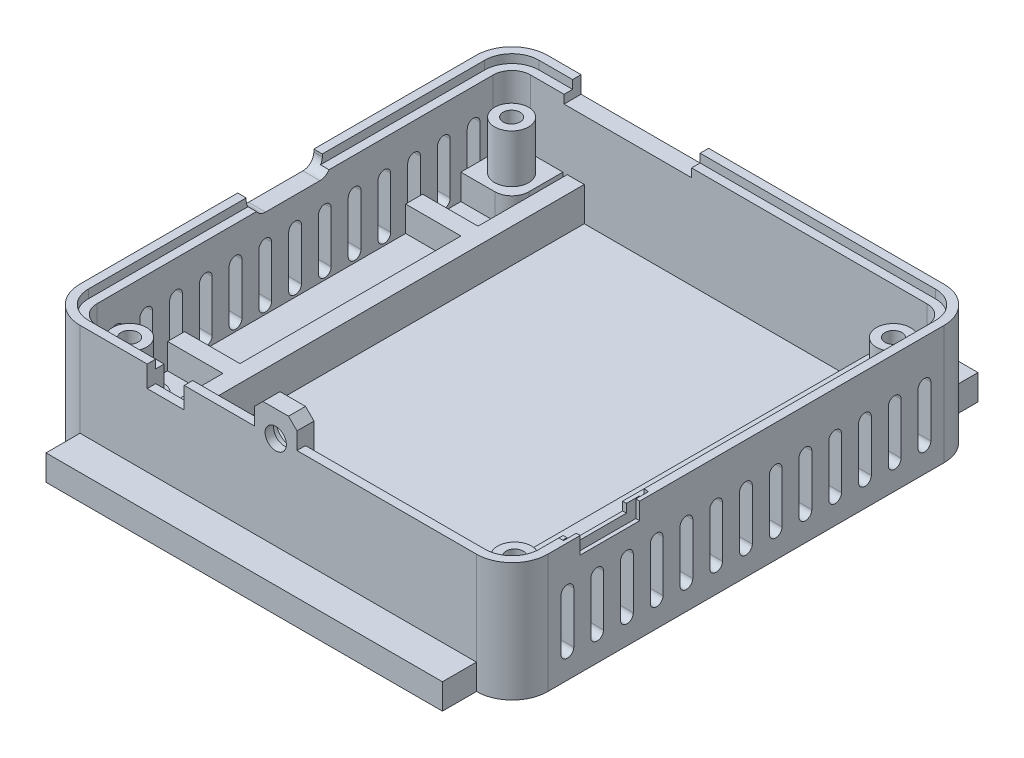
SolidWorks part; units mm, degrees
ref_plane "Front Plane" through (0, 0, 0) normal (0, 0, 1) x (1, 0, 0)
ref_plane "Top Plane" through (0, 0, 0) normal (0, 1, 0) x (1, 0, 0)
ref_plane "Right Plane" through (0, 0, 0) normal (1, 0, 0) x (0, 0, -1)
sketch "Sketch2" plane through (0, 0, 0) normal (0, 1, 0) x (1, 0, 0)
  line L0 (-26.515, 23.3) -> (-26.515, -23.3)
  line L1 (-23.315, 25.5) -> (23.315, 25.5)
  line L2 (-25.515, 23.3) -> (-25.515, -23.3)
  line L3 (-23.315, -25.5) -> (23.315, -25.5)
  line L4 (25.515, 23.3) -> (25.515, -23.3)
  line L5 (-25.515, 25.5) -> (25.515, -25.5) construction
  line L6 (-25.515, -25.5) -> (25.515, 25.5) construction
  line L7 (-23.315, -26.5) -> (23.315, -26.5)
  line L8 (26.515, 23.3) -> (26.515, -23.3)
  line L9 (-23.315, 26.5) -> (23.315, 26.5)
  line L10 (-27.515, 23.3) -> (-27.515, -23.3)
  line L11 (-23.315, -27.5) -> (23.315, -27.5)
  line L12 (27.515, 23.3) -> (27.515, -23.3)
  line L13 (-23.315, 27.5) -> (23.315, 27.5)
  line L14 (-25.515, 19.5) -> (-21.515, 19.5)
  line L15 (-19.515, 21.5) -> (-19.515, 25.5)
  line L16 (19.515, 25.5) -> (19.515, 21.5)
  line L17 (21.515, 19.5) -> (25.515, 19.5)
  line L18 (-25.515, -19.5) -> (-21.515, -19.5)
  line L19 (-19.515, -21.5) -> (-19.515, -25.5)
  line L20 (19.515, -25.5) -> (19.515, -21.5)
  line L21 (21.515, -19.5) -> (25.515, -19.5)
  arc A0 (23.315, 25.5) -> (25.515, 23.3) centre (23.315, 23.3) cw
  arc A1 (25.515, -23.3) -> (23.315, -25.5) centre (23.315, -23.3) cw
  arc A2 (-23.315, -25.5) -> (-25.515, -23.3) centre (-23.315, -23.3) cw
  arc A3 (-23.315, 25.5) -> (-25.515, 23.3) centre (-23.315, 23.3) ccw
  arc A4 (-23.315, -26.5) -> (-26.515, -23.3) centre (-23.315, -23.3) cw
  arc A5 (26.515, -23.3) -> (23.315, -26.5) centre (23.315, -23.3) cw
  arc A6 (23.315, 26.5) -> (26.515, 23.3) centre (23.315, 23.3) cw
  arc A7 (-23.315, 26.5) -> (-26.515, 23.3) centre (-23.315, 23.3) ccw
  arc A8 (-23.315, -27.5) -> (-27.515, -23.3) centre (-23.315, -23.3) cw
  arc A9 (27.515, -23.3) -> (23.315, -27.5) centre (23.315, -23.3) cw
  arc A10 (23.315, 27.5) -> (27.515, 23.3) centre (23.315, 23.3) cw
  arc A11 (-23.315, 27.5) -> (-27.515, 23.3) centre (-23.315, 23.3) ccw
  circle A12 centre (-22.455, 22.41) radius 1
  circle A13 centre (22.445, 22.42) radius 1
  circle A14 centre (22.425, -22.11) radius 1
  circle A15 centre (-22.495, -22.49) radius 1
  arc A20 (21.515, -19.5) -> (19.515, -21.5) centre (21.515, -21.5) ccw
  arc A21 (-19.515, -21.5) -> (-21.515, -19.5) centre (-21.515, -21.5) ccw
  arc A22 (-19.515, 21.5) -> (-21.515, 19.5) centre (-21.515, 21.5) cw
  arc A23 (21.515, 19.5) -> (19.515, 21.5) centre (21.515, 21.5) cw
  point P0 (0, 0)
  point P64 (-20.015, -20)
  point P65 (19.515, -19.5)
  point P67 (20.015, -20)
  point P69 (-19.515, -19.5)
  point P70 (20.015, 20)
  point P73 (-20.015, 20)
  point P74 (-19.515, 19.5)
  point P77 (19.515, 19.5)
  dimension "D3" = 2.2
  dimension "D6" = 3.09
  dimension "D7" = 3.06
  dimension "D8" = 2
  dimension "D9" = 2
  dimension "D10" = 3.07
  dimension "D11" = 3.08
  dimension "D12" = 2
  dimension "D13" = 3.39
  dimension "D14" = 3.09
  dimension "D15" = 3.01
  dimension "D16" = 3.02
  dimension "D17" = 2
  dimension "D28" = 2
  dimension "D29" = 55.03
  dimension "D30" = 55
  dimension "D18" = 6
  dimension "D19" = 6
  dimension "D20" = 6
  dimension "D21" = 6
  dimension "D1" = 51.03
  dimension "D2" = 51
  dimension "D5" = 2
  dimension "D22" = 6
  dimension "D23" = 6
  dimension "D24" = 6
  dimension "D25" = 6
  dimension "D26" = 1
  dimension "D27" = 1
  dimension "D4" = 1
extrude "Boss-Extrude1" add sketch "Sketch2" along normal blind 14 contours L13 A11 L10 A8 L11 A9 L12 A10 A7 L9 A6 L8 A5 L7 A4 L0 region at (-25.7347, 0, -25.7197)
extrude "Boss-Extrude2" add sketch "Sketch2<3>" along normal blind 13 contours L9 A7 L0 A4 L7 A5 L8 A6 A3 L1 A0 L4 A1 L3 A2 L2 region at (-25.0476, 0, -25.0326)
sketch "Sketch2<3>" plane through (0, 0, 0) normal (0, 1, 0) x (1, 0, 0) same geometry as "Sketch2"
extrude "Boss-Extrude4" add sketch "Sketch2<5>" along normal blind 2 contours L2 L3 L4 L1 region at (0, 0, 0)
sketch "Sketch2<5>" plane through (0, 0, 0) normal (0, 1, 0) x (1, 0, 0) same geometry as "Sketch2"
sketch "Sketch4" plane through (0, 0, -27.5) normal (0, 0, -1) x (-1, 0, 0)
  line L0 (23.315, 14) -> (-23.315, 14) construction
  line L1 (19.375, 12) -> (4.375, 12)
  line L2 (19.375, 12) -> (19.375, 14)
  line L3 (19.375, 14) -> (4.375, 14)
  line L4 (4.375, 12) -> (4.375, 14)
  line L5 (19.375, 12) -> (4.375, 14) construction
  line L6 (19.375, 14) -> (4.375, 12) construction
  line L7 (27.515, 14) -> (27.515, 0) construction
  point P0 (11.875, 13)
  dimension "D1" = 8.14
  dimension "D2" = 15
  dimension "D3" = 2
extrude "Cut-Extrude1" cut sketch "Sketch4" against normal blind 2
sketch "Sketch6" plane through (-27.515, 0, 0) normal (-1, 0, 0) x (0, 0, 1)
  line L0 (-23.3, 14) -> (23.3, 14) construction
  line L1 (-4.2, 14) -> (4.75, 14)
  line L2 (-4.2, 14) -> (-4.2, 13.7)
  line L3 (-2.92, 12.42) -> (3.47, 12.42)
  line L4 (4.75, 14) -> (4.75, 13.7)
  line L5 (-27.5, 14) -> (-27.5, 0) construction
  line L6 (27.5, 14) -> (27.5, 0) construction
  arc A0 (4.75, 13.7) -> (3.47, 12.42) centre (3.47, 13.7) cw
  arc A1 (-2.92, 12.42) -> (-4.2, 13.7) centre (-2.92, 13.7) cw
  point P10 (4.75, 12.42)
  point P13 (-4.2, 12.42)
  dimension "D4" = 1.28
  dimension "D1" = 23.3
  dimension "D2" = 1.58
  dimension "D3" = 8.95
  dimension "D5" = 22.75
extrude "Cut-Extrude3" cut sketch "Sketch6" against normal blind 2
sketch "Sketch7" plane through (0, 0, 27.5) normal (0, 0, 1) x (1, 0, 0)
  line L0 (-23.315, 0) -> (23.315, 0) construction
  line L1 (27.515, 14) -> (27.515, 0) construction
  line L2 (0, 0) -> (0, 27.9568) construction
  line L3 (-27.515, 14) -> (-27.515, 0) construction
  circle A0 centre (-0.29, 13.97) radius 1.25
  dimension "D1" = 27.225
  dimension "D2" = 2.5
  dimension "D3" = 13.97
  dimension "D4" = 27.805
extrude "Cut-Extrude4" cut sketch "Sketch7" against normal blind 2
sketch "Sketch8" plane through (0, 0, 25.5) normal (0, 0, -1) x (-1, 0, 0)
  circle A0 centre (0.29, 13.97) radius 2
  dimension "D1" = 4
sketch "Sketch9" plane through (0, 2, 0) normal (0, 1, 0) x (1, 0, 0)
  line L0 (-17, 25.5) -> (-17, -25.5)
  line L1 (-19.515, 25.5) -> (19.515, 25.5) construction
  line L2 (-19.515, -25.5) -> (19.515, -25.5) construction
  line L3 (17, 25.5) -> (17, -25.5)
  line L4 (-25.515, 19.5) -> (-25.515, -19.5) construction
  line L5 (25.515, 19.5) -> (25.515, -19.5) construction
  line L6 (-19, 25.5) -> (-19, 15)
  line L7 (19, 25.5) -> (19, 15)
  line L8 (-19, 25.5) -> (-17, 25.5)
  line L9 (-19, -25.5) -> (-17, -25.5)
  line L10 (17, -25.5) -> (19, -25.5)
  line L11 (17, 25.5) -> (19, 25.5)
  line L13 (-25.515, 19.5) -> (-25.515, -19.5) construction
  line L14 (-25.515, 15) -> (-19, 15)
  line L15 (-25.515, 15) -> (-25.515, 13)
  line L16 (-25.515, 13) -> (-19, 13)
  line L17 (25.515, 15) -> (25.515, 13)
  line L18 (25.515, 23.3) -> (25.515, -23.3) construction
  line L19 (-25.515, -4.5416) -> (-25.515, -23.3) construction
  line L20 (-25.515, -13) -> (-19, -13)
  line L21 (-25.515, -13) -> (-25.515, -15)
  line L22 (-25.515, -15) -> (-19, -15)
  line L23 (25.515, -13) -> (25.515, -15)
  line L24 (19, 15) -> (25.515, 15)
  line L25 (19, 13) -> (25.515, 13)
  line L26 (19, -13) -> (25.515, -13)
  line L27 (19, -15) -> (25.515, -15)
  line L28 (-19.515, 25.5) -> (19.515, 25.5) construction
  line L29 (-19.515, -25.5) -> (19.515, -25.5) construction
  line L30 (-4.375, 25.5) -> (23.315, 25.5) construction
  line L31 (-19, 13) -> (-19, -13)
  line L32 (-19, 25.5) -> (-19, -25.5) construction
  line L33 (-19, -15) -> (-19, -25.5)
  line L34 (19, -15) -> (19, -25.5)
  line L35 (19, 25.5) -> (19, -25.5) construction
  line L36 (19, 13) -> (19, -13)
  dimension "D1" = 34
  dimension "D2" = 8.515
  dimension "D3" = 8.515
  dimension "D6" = 2
  dimension "D7" = 2
  dimension "D8" = 2
  dimension "D9" = 2
  dimension "D10" = 10.5
  dimension "D11" = 10.5
  dimension "D12" = 26
  dimension "D13" = 10.5
  dimension "D14" = 26
  dimension "D15" = 10.5
  dimension "D4" = 2
  dimension "D5" = 2
extrude "Boss-Extrude6" add sketch "Sketch9" along normal blind 3
extrude "Boss-Extrude9" add sketch "Sketch2<7>" along normal blind 5 contours A12 | A13 | A15 | A14 region at (-21.415, 0, -25.4151) region at (21.415, 0, -25.4151) region at (-23.515, 0, 19.5849) region at (25.4301, 0, 21.4)
sketch "Sketch2<7>" plane through (0, 0, 0) normal (0, 1, 0) x (1, 0, 0) same geometry as "Sketch2"
sketch "Sketch11" plane through (0, 5, 0) normal (0, 1, 0) x (1, 0, 0)
  circle A0 centre (-22.455, 22.41) radius 1
  circle A1 centre (-22.455, 22.41) radius 2
  circle A2 centre (22.445, 22.42) radius 1
  circle A3 centre (22.445, 22.42) radius 2
  circle A6 centre (-22.495, -22.49) radius 1
  circle A7 centre (-22.495, -22.49) radius 2
  circle A8 centre (22.425, -22.11) radius 1
  circle A9 centre (22.425, -22.11) radius 2
  dimension "D1" = 2
  dimension "D2" = 4
  dimension "D3" = 2
  dimension "D4" = 4
  dimension "D5" = 2
  dimension "D6" = 4
  dimension "D7" = 2
  dimension "D8" = 4
extrude "Boss-Extrude10" add sketch "Sketch11" along normal blind 5.68
sketch "Sketch13" plane through (0, 0, 27.5) normal (0, 0, 1) x (1, 0, 0)
  line L0 (27.515, 14) -> (27.515, 0) construction
  line L5 (-27.515, 14) -> (-27.515, 0) construction
  line L7 (0.9596, 14) -> (23.315, 14) construction
  line L8 (-2.79, 17) -> (2.21, 17)
  line L9 (-2.79, 17) -> (-2.79, 14)
  line L10 (-2.79, 14) -> (-1.5396, 14)
  line L11 (2.21, 17) -> (2.21, 14)
  line L12 (-2.79, 17) -> (2.21, 14) construction
  line L13 (-2.79, 14) -> (2.21, 17) construction
  line L14 (0.9596, 14) -> (2.21, 14)
  arc A0 (0.9596, 14) -> (-1.5396, 14) centre (-0.29, 13.97) ccw
  point P0 (-0.29, 15.5)
  dimension "D4" = 0.03
  dimension "D5" = 2.5
  dimension "D7" = 2.5
  dimension "D1" = 5
  dimension "D2" = 25.305
  dimension "D3" = 3
  dimension "D6" = 24.725
extrude "Boss-Extrude11" add sketch "Sketch13" against normal blind 2
sketch "Sketch15" plane through (0, 0, 26.5) normal (0, 0, -1) x (-1, 0, 0)
  line L0 (-1.459, 13) -> (-1.459, 14)
  line L1 (-2.21, 14) -> (-2.21, 13)
  line L2 (-2.21, 13) -> (-1.459, 13)
  line L3 (-1.459, 14) -> (-2.21, 14)
  line L4 (2.039, 13) -> (2.039, 14)
  line L5 (2.79, 14) -> (2.79, 13)
  line L6 (2.039, 14) -> (2.79, 14)
  line L7 (2.79, 13) -> (2.039, 13)
  dimension "D1" = 1
  dimension "D2" = 1
  dimension "D3" = 0.751
  dimension "D4" = 1
  dimension "D5" = 1
  dimension "D6" = 0.751
extrude "Boss-Extrude13" add sketch "Sketch15" along normal blind 1
extrude "Cut-Extrude5" cut sketch "Sketch8" against normal blind 1
sketch "Sketch16" plane through (0, 2, 0) normal (0, 1, 0) x (1, 0, 0)
  line L1 (-17, 25.5) -> (17, 25.5)
  line L2 (-17, 25.5) -> (-17, -25.5)
  line L3 (-17, -25.5) -> (17, -25.5)
  line L4 (17, 25.5) -> (17, -25.5)
  line L5 (-17, 25.5) -> (17, -25.5) construction
  line L6 (-17, -25.5) -> (17, 25.5) construction
  point P0 (0, 0)
extrude "Cut-Extrude6" cut sketch "Sketch16" against normal blind 1
sketch "Sketch17" plane through (0, 0, 0) normal (0, -1, 0) x (1, 0, 0)
  circle A0 centre (-22.495, 22.49) radius 2
  circle A1 centre (22.425, 22.11) radius 2
  circle A2 centre (-22.455, -22.41) radius 2
  circle A3 centre (22.445, -22.42) radius 2
  dimension "D1" = 4
  dimension "D2" = 4
  dimension "D3" = 4
  dimension "D4" = 4
extrude "Cut-Extrude7" cut sketch "Sketch17" against normal blind 3
sketch "Sketch19" plane through (27.515, 0, 0) normal (1, 0, 0) x (0, 0, -1)
  line L0 (23.3, 14) -> (-23.3, 14) construction
  line L2 (-21.75, 9) -> (-21.75, 3)
  line L4 (-20.25, 9) -> (-20.25, 3)
  line L5 (-27.5, 14) -> (-27.5, 0) construction
  line L6 (23.3, 0) -> (-23.3, 0) construction
  line L7 (-18.25, 9) -> (-18.25, 3)
  line L8 (-16.75, 9) -> (-16.75, 3)
  line L9 (-14.75, 9) -> (-14.75, 3)
  line L10 (-13.25, 9) -> (-13.25, 3)
  line L11 (-11.25, 9) -> (-11.25, 3)
  line L12 (-9.75, 9) -> (-9.75, 3)
  line L13 (-7.75, 9) -> (-7.75, 3)
  line L14 (-6.25, 9) -> (-6.25, 3)
  line L15 (-4.25, 9) -> (-4.25, 3)
  line L16 (-2.75, 9) -> (-2.75, 3)
  line L17 (-0.75, 9) -> (-0.75, 3)
  line L18 (0.75, 9) -> (0.75, 3)
  line L19 (2.75, 9) -> (2.75, 3)
  line L20 (4.25, 9) -> (4.25, 3)
  line L21 (6.25, 9) -> (6.25, 3)
  line L22 (7.75, 9) -> (7.75, 3)
  line L23 (9.75, 9) -> (9.75, 3)
  line L24 (11.25, 9) -> (11.25, 3)
  line L25 (13.25, 9) -> (13.25, 3)
  line L26 (14.75, 9) -> (14.75, 3)
  line L27 (16.75, 9) -> (16.75, 3)
  line L28 (18.25, 9) -> (18.25, 3)
  line L29 (20.25, 9) -> (20.25, 3)
  line L30 (21.75, 9) -> (21.75, 3)
  line L31 (27.5, 14) -> (27.5, 0) construction
  arc A0 (-21.75, 9) -> (-20.25, 9) centre (-21, 9) cw
  arc A1 (-21.75, 3) -> (-20.25, 3) centre (-21, 3) ccw
  arc A2 (-18.25, 3) -> (-16.75, 3) centre (-17.5, 3) ccw
  arc A3 (-18.25, 9) -> (-16.75, 9) centre (-17.5, 9) cw
  arc A4 (-14.75, 3) -> (-13.25, 3) centre (-14, 3) ccw
  arc A5 (-14.75, 9) -> (-13.25, 9) centre (-14, 9) cw
  arc A6 (-11.25, 3) -> (-9.75, 3) centre (-10.5, 3) ccw
  arc A7 (-11.25, 9) -> (-9.75, 9) centre (-10.5, 9) cw
  arc A8 (-7.75, 3) -> (-6.25, 3) centre (-7, 3) ccw
  arc A9 (-7.75, 9) -> (-6.25, 9) centre (-7, 9) cw
  arc A10 (-4.25, 3) -> (-2.75, 3) centre (-3.5, 3) ccw
  arc A11 (-4.25, 9) -> (-2.75, 9) centre (-3.5, 9) cw
  arc A12 (-0.75, 3) -> (0.75, 3) centre (0, 3) ccw
  arc A13 (-0.75, 9) -> (0.75, 9) centre (0, 9) cw
  arc A14 (2.75, 3) -> (4.25, 3) centre (3.5, 3) ccw
  arc A15 (2.75, 9) -> (4.25, 9) centre (3.5, 9) cw
  arc A16 (6.25, 3) -> (7.75, 3) centre (7, 3) ccw
  arc A17 (6.25, 9) -> (7.75, 9) centre (7, 9) cw
  arc A18 (9.75, 3) -> (11.25, 3) centre (10.5, 3) ccw
  arc A19 (9.75, 9) -> (11.25, 9) centre (10.5, 9) cw
  arc A20 (13.25, 3) -> (14.75, 3) centre (14, 3) ccw
  arc A21 (13.25, 9) -> (14.75, 9) centre (14, 9) cw
  arc A22 (16.75, 3) -> (18.25, 3) centre (17.5, 3) ccw
  arc A23 (16.75, 9) -> (18.25, 9) centre (17.5, 9) cw
  arc A24 (20.25, 3) -> (21.75, 3) centre (21, 3) ccw
  arc A25 (20.25, 9) -> (21.75, 9) centre (21, 9) cw
  dimension "D3" = 0.75
  dimension "D1" = 6
  dimension "D2" = 1.5
  dimension "D4" = 5
  dimension "D5" = 5.75
  dimension "D6" = 3
  dimension "D8" = 5.75
  dimension "D7" = 13
extrude "Cut-Extrude9" cut sketch "Sketch19" against normal blind 2
sketch "Sketch20" plane through (-27.515, 0, 0) normal (-1, 0, 0) x (0, 0, 1)
  line L0 (-23.3, 14) -> (-4.2, 14) construction
  line L2 (-21.75, 9) -> (-21.75, 3)
  line L4 (-20.25, 9) -> (-20.25, 3)
  line L5 (-23.3, 0) -> (23.3, 0) construction
  line L6 (-27.5, 14) -> (-27.5, 0) construction
  line L7 (-18.25, 9) -> (-18.25, 3)
  line L8 (-16.75, 9) -> (-16.75, 3)
  line L9 (-14.75, 9) -> (-14.75, 3)
  line L10 (-13.25, 9) -> (-13.25, 3)
  line L11 (-11.25, 9) -> (-11.25, 3)
  line L12 (-9.75, 9) -> (-9.75, 3)
  line L13 (-7.75, 9) -> (-7.75, 3)
  line L14 (-6.25, 9) -> (-6.25, 3)
  line L15 (-4.25, 9) -> (-4.25, 3)
  line L16 (-2.75, 9) -> (-2.75, 3)
  line L17 (-0.75, 9) -> (-0.75, 3)
  line L18 (0.75, 9) -> (0.75, 3)
  line L19 (2.75, 9) -> (2.75, 3)
  line L20 (4.25, 9) -> (4.25, 3)
  line L21 (6.25, 9) -> (6.25, 3)
  line L22 (7.75, 9) -> (7.75, 3)
  line L23 (9.75, 9) -> (9.75, 3)
  line L24 (11.25, 9) -> (11.25, 3)
  line L25 (13.25, 9) -> (13.25, 3)
  line L26 (14.75, 9) -> (14.75, 3)
  line L27 (16.75, 9) -> (16.75, 3)
  line L28 (18.25, 9) -> (18.25, 3)
  line L29 (20.25, 9) -> (20.25, 3)
  line L30 (21.75, 9) -> (21.75, 3)
  line L31 (27.5, 14) -> (27.5, 0) construction
  arc A0 (-21.75, 9) -> (-20.25, 9) centre (-21, 9) cw
  arc A1 (-21.75, 3) -> (-20.25, 3) centre (-21, 3) ccw
  arc A2 (-18.25, 3) -> (-16.75, 3) centre (-17.5, 3) ccw
  arc A3 (-18.25, 9) -> (-16.75, 9) centre (-17.5, 9) cw
  arc A4 (-14.75, 3) -> (-13.25, 3) centre (-14, 3) ccw
  arc A5 (-14.75, 9) -> (-13.25, 9) centre (-14, 9) cw
  arc A6 (-11.25, 3) -> (-9.75, 3) centre (-10.5, 3) ccw
  arc A7 (-11.25, 9) -> (-9.75, 9) centre (-10.5, 9) cw
  arc A8 (-7.75, 3) -> (-6.25, 3) centre (-7, 3) ccw
  arc A9 (-7.75, 9) -> (-6.25, 9) centre (-7, 9) cw
  arc A10 (-4.25, 3) -> (-2.75, 3) centre (-3.5, 3) ccw
  arc A11 (-4.25, 9) -> (-2.75, 9) centre (-3.5, 9) cw
  arc A12 (-0.75, 3) -> (0.75, 3) centre (0, 3) ccw
  arc A13 (-0.75, 9) -> (0.75, 9) centre (0, 9) cw
  arc A14 (2.75, 3) -> (4.25, 3) centre (3.5, 3) ccw
  arc A15 (2.75, 9) -> (4.25, 9) centre (3.5, 9) cw
  arc A16 (6.25, 3) -> (7.75, 3) centre (7, 3) ccw
  arc A17 (6.25, 9) -> (7.75, 9) centre (7, 9) cw
  arc A18 (9.75, 3) -> (11.25, 3) centre (10.5, 3) ccw
  arc A19 (9.75, 9) -> (11.25, 9) centre (10.5, 9) cw
  arc A20 (13.25, 3) -> (14.75, 3) centre (14, 3) ccw
  arc A21 (13.25, 9) -> (14.75, 9) centre (14, 9) cw
  arc A22 (16.75, 3) -> (18.25, 3) centre (17.5, 3) ccw
  arc A23 (16.75, 9) -> (18.25, 9) centre (17.5, 9) cw
  arc A24 (20.25, 3) -> (21.75, 3) centre (21, 3) ccw
  arc A25 (20.25, 9) -> (21.75, 9) centre (21, 9) cw
  dimension "D1" = 1.5
  dimension "D2" = 6
  dimension "D3" = 5
  dimension "D4" = 3
  dimension "D5" = 5.75
  dimension "D7" = 5.75
  dimension "D6" = 13
extrude "Cut-Extrude10" cut sketch "Sketch20" against normal blind 2
sketch "Sketch21" plane through (0, 0, 27.5) normal (0, 0, 1) x (1, 0, 0)
  line L0 (-23.315, 14) -> (-2.79, 14) construction
  line L1 (-15.415, 14) -> (-11.055, 14)
  line L2 (-15.415, 14) -> (-15.415, 11.5)
  line L3 (-15.415, 11.5) -> (-11.055, 11.5)
  line L4 (-11.055, 14) -> (-11.055, 11.5)
  line L5 (-27.515, 14) -> (-27.515, 0) construction
  dimension "D1" = 12.1
  dimension "D2" = 4.36
  dimension "D3" = 2.5
extrude "Cut-Extrude11" cut sketch "Sketch21" against normal blind 2
sketch "Sketch23" plane through (0, 0, 25.5) normal (0, 0, -1) x (-1, 0, 0)
  line L1 (11.055, 11.5) -> (15.415, 11.5)
  line L2 (11.055, 11.5) -> (11.055, 5)
  line L3 (11.055, 5) -> (15.415, 5)
  line L4 (15.415, 11.5) -> (15.415, 5)
  dimension "D1" = 4.36
  dimension "D2" = 6.5
extrude "Cut-Extrude12" cut sketch "Sketch23" against normal blind 1
sketch "Sketch24" plane through (27.515, 0, 0) normal (1, 0, 0) x (0, 0, -1)
  line L0 (23.3, 14) -> (-23.3, 14) construction
  line L1 (-19.5, 14) -> (-12.5, 14)
  line L2 (-19.5, 14) -> (-19.5, 12)
  line L3 (-19.5, 12) -> (-12.5, 12)
  line L4 (-12.5, 14) -> (-12.5, 12)
  line L5 (-27.5, 14) -> (-27.5, 0) construction
  dimension "D1" = 2
  dimension "D2" = 7
  dimension "D3" = 8
extrude "Cut-Extrude13" cut sketch "Sketch24" against normal blind 2
sketch "Sketch26" plane through (0, 14, 0) normal (0, 1, 0) x (1, 0, 0)
  line L0 (27.515, -12.5) -> (26.515, -12.5) construction
  line L1 (25.965, -11) -> (27.065, -11)
  line L2 (25.965, -11) -> (25.965, -21)
  line L3 (25.965, -21) -> (27.065, -21)
  line L4 (27.065, -11) -> (27.065, -21)
  line L5 (25.515, -19.5) -> (26.515, -19.5) construction
  line L6 (25.515, 23.3) -> (25.515, -12.5) construction
  line L7 (27.515, 23.3) -> (27.515, -12.5) construction
  dimension "D1" = 1.5
  dimension "D2" = 1.1
  dimension "D3" = 10
  dimension "D4" = 1.5
  dimension "D5" = 0.45
  dimension "D6" = 0.45
extrude "Cut-Extrude14" cut sketch "Sketch26" against normal blind 4
chamfer "Chamfer1" distance 1 angle 45 2 edges at (-2.79, 17, 26.5) (2.21, 17, 26.5)
sketch "Sketch28" plane through (0, 0, 27.5) normal (0, 0, 1) x (1, 0, 0)
  line L5 (23.315, 14) -> (23.315, 0) construction
  line L6 (-23.315, 0) -> (23.315, 0)
  line L7 (-23.315, 0) -> (-23.315, 3)
  line L8 (-23.315, 3) -> (23.315, 3)
  line L9 (23.315, 0) -> (23.315, 3)
  dimension "D1" = 3
extrude "Boss-Extrude14" add sketch "Sketch28" along normal blind 4
sketch "Sketch29" plane through (0, 0, -27.5) normal (0, 0, -1) x (-1, 0, 0)
  line L0 (23.315, 14) -> (23.315, 0) construction
  line L1 (-23.315, 0) -> (23.315, 0)
  line L2 (-23.315, 0) -> (-23.315, 3)
  line L3 (-23.315, 3) -> (23.315, 3)
  line L4 (23.315, 0) -> (23.315, 3)
  dimension "D1" = 3
extrude "Boss-Extrude15" add sketch "Sketch29" along normal blind 4
